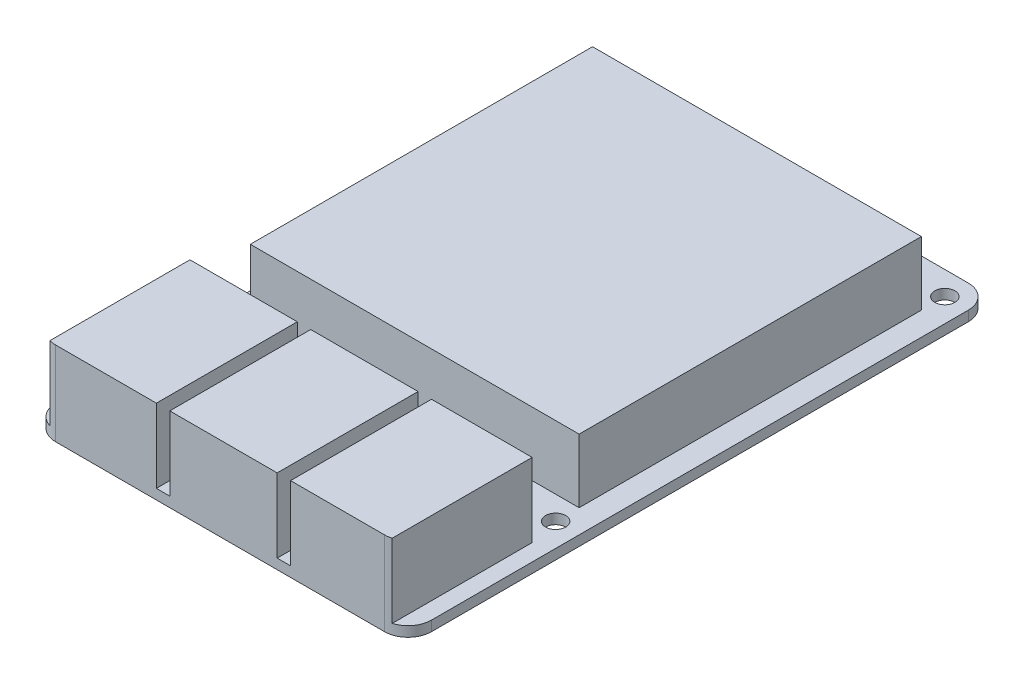
SolidWorks part; units mm, degrees
ref_plane "Спереди" through (0, 0, 0) normal (0, 0, 1) x (1, 0, 0)
ref_plane "Сверху" through (0, 0, 0) normal (0, 1, 0) x (1, 0, 0)
ref_plane "Справа" through (0, 0, 0) normal (1, 0, 0) x (0, 0, -1)
sketch "Эскиз1" plane through (0, 0, 0) normal (0, 1, 0) x (1, 0, 0)
  line L0 (3.5, 0) -> (52.5, 0)
  line L1 (0, 3.5) -> (0, 83.5)
  line L2 (3.5, 87) -> (52.5, 87)
  line L3 (56, 83.5) -> (56, 3.5)
  line L4 (3.5, 83.5) -> (3.5, 25.5) construction
  line L5 (3.5, 25.5) -> (52.5, 25.5) construction
  arc A0 (52.5, 87) -> (56, 83.5) centre (52.5, 83.5) cw
  arc A1 (52.5, 0) -> (56, 3.5) centre (52.5, 3.5) ccw
  arc A2 (3.5, 0) -> (0, 3.5) centre (3.5, 3.5) cw
  arc A3 (0, 83.5) -> (3.5, 87) centre (3.5, 83.5) cw
  circle A4 centre (3.5, 83.5) radius 1.5
  circle A5 centre (52.5, 83.5) radius 1.5
  circle A6 centre (52.5, 25.5) radius 1.5
  circle A7 centre (3.5, 25.5) radius 1.5
  point P11 (0, 0)
  dimension "D1" = 3.5
extrude "Бобышка-Вытянуть1" add sketch "Эскиз1" along normal blind 1.5
sketch "Эскиз2" plane through (0, 1.5, 0) normal (0, 1, 0) x (1, 0, 0)
  line L0 (28, 0) -> (20.5, 0)
  line L1 (3.5, 0) -> (52.5, 0) construction
  line L2 (2.5, 0) -> (2.5, 21)
  line L3 (2.5, 21) -> (18.5, 21)
  line L4 (53.5, 21) -> (53.5, 0)
  line L5 (53.5, 0) -> (38.5, 0)
  line L6 (2.5, 21) -> (18.5, 21)
  line L7 (18.5, 21) -> (18.5, 0)
  line L9 (20.5, 0) -> (20.5, 21)
  line L10 (20.5, 21) -> (36.5, 21)
  line L11 (36.5, 21) -> (36.5, 0)
  line L13 (38.5, 0) -> (38.5, 21)
  line L14 (20.5, 21) -> (36.5, 21)
  line L15 (38.5, 21) -> (53.5, 21)
  line L16 (36.5, 0) -> (28, 0)
  line L17 (18.5, 0) -> (2.5, 0)
  arc M7 (0, 3.5) -> (3.5, 0) centre (3.5, 3.5) ccw
  line M8 (3.5, 0) -> (52.5, 0)
  arc M9 (52.5, 0) -> (56, 3.5) centre (52.5, 3.5) ccw
extrude "Бобышка-Вытянуть2" add sketch "Эскиз2" along normal blind 11 contours L7 L3 L2 M7 M8 | L11 L10 L9 M8 | L15 L13 L4 M8 M9 region at (10.5011, 1.5, -10.5015) region at (45.9989, 1.5, -10.5016) region at (28.5, 1.5, -10.5)
sketch "Эскиз3" plane through (0, 1.5, 0) normal (0, 1, 0) x (1, 0, 0)
  line L1 (52.5, 80) -> (3.5, 80)
  line L2 (3.5, 80) -> (3.5, 29)
  line L3 (3.5, 29) -> (52.5, 29)
  line L4 (52.5, 29) -> (52.5, 80)
extrude "Бобышка-Вытянуть3" add sketch "Эскиз3" along normal blind 9.5
